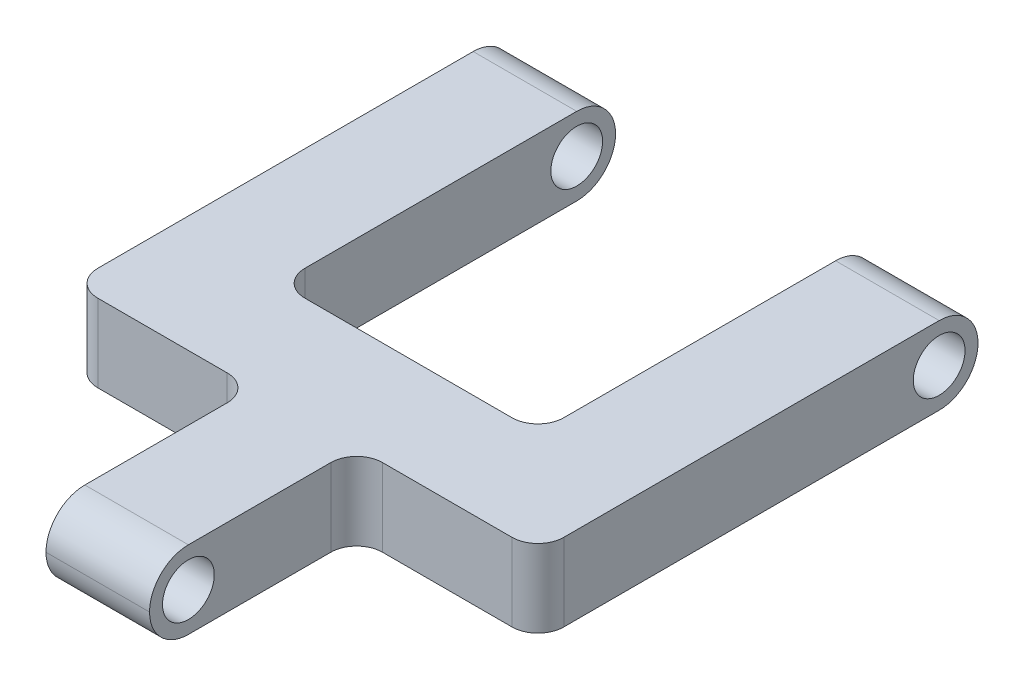
SolidWorks part; units mm, degrees
ref_plane "Front Plane" through (0, 0, 0) normal (0, 0, 1) x (1, 0, 0)
ref_plane "Top Plane" through (0, 0, 0) normal (0, 1, 0) x (1, 0, 0)
ref_plane "Right Plane" through (0, 0, 0) normal (1, 0, 0) x (0, 0, -1)
sketch "Sketch1" plane through (0, 0, 0) normal (0, 1, 0) x (1, 0, 0)
  line L0 (-4, 0) -> (4, 0)
  line L1 (4, 0) -> (4, 16)
  line L2 (4, 16) -> (18, 16)
  line L3 (18, 16) -> (18, 50)
  line L4 (18, 50) -> (10, 50)
  line L5 (10, 50) -> (10, 24)
  line L6 (10, 24) -> (-10, 24)
  line L7 (-10, 24) -> (-10, 50)
  line L8 (-10, 50) -> (-18, 50)
  line L9 (-18, 50) -> (-18, 16)
  line L10 (-18, 16) -> (-4, 16)
  line L11 (-4, 16) -> (-4, 0)
  point P7 (0, 24)
  dimension "D1" = 8
  dimension "D2" = 50
  dimension "D3" = 8
  dimension "D4" = 20
  dimension "D5" = 16
extrude "Boss-Extrude1" add sketch "Sketch1" along normal blind 6
fillet "Fillet1" radius 3 6 edges at (0, 0, 0) (0, 6, 0) (-14, 6, -50) (-14, 0, -50) (14, 0, -50) (14, 6, -50)
fillet "Fillet2" radius 2 6 edges at (-18, 3, -16) (-4, 3, -16) (4, 3, -16) (18, 3, -16) (-10, 3, -24) (10, 3, -24)
hole_wizard "Ø4.0 mm Dowel Holes1" positions "Sketch2" profile "Sketch3" hole size "Ø4.0" standard "ISO" end condition through all
sketch "Sketch2" plane through (-18, 0, 0) normal (-1, 0, 0) x (0, 0, 1)
  point P0 (-47, 3)
sketch "Sketch3" plane through (-18, 3, -47) normal (0, 1, 0) x (0, 0, 1)
  line L0 (0, 0) -> (0, 36)
  line L1 (0, 36) -> (2, 36)
  line L2 (2, 36) -> (2, 0)
  line L5 (2, 0) -> (0, 0)
  line L11 (0, -6.35) -> (0, 107.95) construction
  dimension "Thru Hole Dia." = 4
  dimension "Thru Hole Depth" = 36
hole_wizard "Ø4.0 mm Dowel Holes2" positions "Sketch6" profile "Sketch7" hole size "Ø4.0" standard "ISO" end condition through all
sketch "Sketch6" plane through (-4, 0, 0) normal (-1, 0, 0) x (0, 0, 1)
  point P0 (-3, 3)
sketch "Sketch7" plane through (-4, 3, -3) normal (0, 1, 0) x (0, 0, 1)
  line L0 (0, 0) -> (0, 22)
  line L1 (0, 22) -> (2, 22)
  line L2 (2, 22) -> (2, 0)
  line L5 (2, 0) -> (0, 0)
  line L11 (0, -6.35) -> (0, 107.95) construction
  dimension "Thru Hole Dia." = 4
  dimension "Thru Hole Depth" = 22
